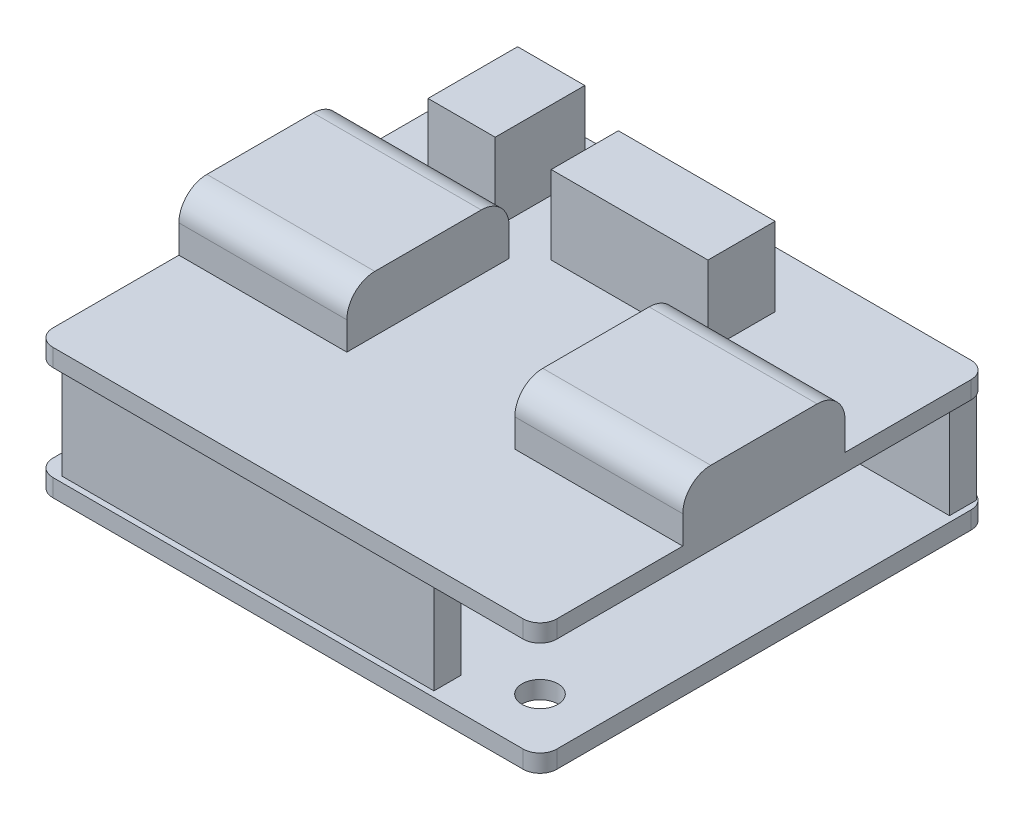
SolidWorks part; units mm, degrees
ref_plane "Front Plane" through (0, 0, 0) normal (0, 0, 1) x (1, 0, 0)
ref_plane "Top Plane" through (0, 0, 0) normal (0, 1, 0) x (1, 0, 0)
ref_plane "Right Plane" through (0, 0, 0) normal (1, 0, 0) x (0, 0, -1)
sketch "Sketch1" plane through (0, 0, 0) normal (0, 1, 0) x (1, 0, 0)
  line L1 (-22.5, -20) -> (22.5, -20)
  line L2 (-22.5, -20) -> (-22.5, 20)
  line L3 (-22.5, 20) -> (22.5, 20)
  line L4 (22.5, -20) -> (22.5, 20)
  line L5 (-22.5, -20) -> (22.5, 20) construction
  line L6 (-22.5, 20) -> (22.5, -20) construction
  point P0 (0, 0)
  dimension "D1" = 45
  dimension "D2" = 40
extrude "Boss-Extrude1" add sketch "Sketch1" along normal blind 1.57
sketch "Sketch2" plane through (0, 1.57, 0) normal (0, 1, 0) x (1, 0, 0)
  line L0 (-21.19, -20) -> (-21.19, 20) construction
  line L1 (21.99, 19.49) -> (-3.92, 19.49)
  line L2 (21.99, 19.49) -> (21.99, 17.08)
  line L3 (21.99, 17.08) -> (-3.92, 17.08)
  line L4 (-3.92, 19.49) -> (-3.92, 17.08)
  line L5 (12.52, -17.08) -> (-20.68, -17.08)
  line L6 (12.52, -17.08) -> (12.52, -19.49)
  line L7 (12.52, -19.49) -> (-20.68, -19.49)
  line L8 (-20.68, -17.08) -> (-20.68, -19.49)
  line L9 (-22.5, -20) -> (22.5, -20) construction
  line L10 (22.5, 20) -> (-22.5, 20) construction
  line L11 (22.5, -20) -> (22.5, 20) construction
  circle A0 centre (17.5, -15) radius 3.2 construction
  dimension "D6" = 6.4
  dimension "D1" = 2.41
  dimension "D2" = 2.41
  dimension "D3" = 33.2
  dimension "D4" = 25.91
  dimension "D5" = 43.69
  dimension "D7" = 5
  dimension "D8" = 5
  dimension "D9" = 0.51
  dimension "D10" = 0.51
  dimension "D11" = 0.51
  dimension "D12" = 0.51
extrude "Boss-Extrude2" add sketch "Sketch2" along normal blind 8.5
sketch "Sketch3" plane through (0, 10.07, 0) normal (0, 1, 0) x (1, 0, 0)
  line L0 (22.5, 20) -> (-22.5, 20) construction
  line L1 (22.5, -20) -> (-22.5, -20)
  line L2 (22.5, -20) -> (22.5, 20)
  line L3 (22.5, 20) -> (-22.5, 20)
  line L4 (-22.5, -20) -> (-22.5, 20)
  dimension "D1" = 45
extrude "Boss-Extrude3" add sketch "Sketch3" along normal blind 1.57
sketch "Sketch4" plane through (0, 11.64, 0) normal (0, 1, 0) x (1, 0, 0)
  line L0 (12.52, -17.08) -> (-20.68, -17.08)
  line L1 (12.52, -17.08) -> (12.52, -19.49)
  line L2 (12.52, -19.49) -> (-20.68, -19.49)
  line L3 (-20.68, -17.08) -> (-20.68, -19.49)
  line L4 (-22.5, -20) -> (22.5, -20) construction
  line L5 (22.5, -20) -> (22.5, 20) construction
  dimension "D1" = 0.51
  dimension "D2" = 2.41
  dimension "D3" = 33.2
  dimension "D4" = 9.98
extrude "Boss-Extrude4" [suppressed] add sketch "Sketch4" along normal blind 8.51
sketch "Sketch5" plane through (0, 11.64, 0) normal (0, 1, 0) x (1, 0, 0)
  line L0 (-22.5, 20) -> (-22.5, -20) construction
  line L1 (-22.5, -7.25) -> (-7.5, -7.25)
  line L2 (-22.5, -7.25) -> (-22.5, 7.25)
  line L3 (-22.5, 7.25) -> (-7.5, 7.25)
  line L4 (-7.5, -7.25) -> (-7.5, 7.25)
  line L5 (-11.0825, 0) -> (11.0825, 0) construction
  point P6 (-7.5, 0)
  dimension "D1" = 14.5
  dimension "D2" = 15
extrude "Boss-Extrude5" add sketch "Sketch5" along normal blind 5
fillet "Fillet1" radius 2.5 2 edges at (-15, 16.64, -7.25) (-15, 16.64, 7.25)
mirror "Mirror1" about plane through (0, 0, 0) normal (1, 0, 0) of "Fillet1", "Boss-Extrude5"
sketch "Sketch7" plane through (0, 1.57, 0) normal (0, 1, 0) x (1, 0, 0)
  line L0 (-22.5, -20) -> (22.5, -20) construction
  line L1 (22.5, -20) -> (22.5, -7.25) construction
  line L2 (-22.5, 20) -> (-22.5, 7.25) construction
  line L3 (22.5, 20) -> (-22.5, 20) construction
  circle A0 centre (17.5, -15) radius 1.6
  circle A1 centre (-17.5, 15) radius 1.6
  dimension "D3" = 3.2
  dimension "D6" = 3.2
  dimension "D1" = 5
  dimension "D2" = 5
  dimension "D4" = 5
  dimension "D5" = 5
extrude "Cut-Extrude1" cut sketch "Sketch7" against normal up to next (1.57 mm away)
fillet "Fillet2" radius 1.5 4 edges at (-22.5, 0.785, -20) (-22.5, 0.785, 20) (22.5, 0.785, 20) (22.5, 0.785, -20)
fillet "Fillet3" radius 1.5 4 edges at (-22.5, 10.855, -20) (22.5, 10.855, 20) (22.5, 10.855, -20) (-22.5, 10.855, 20)
sketch "Sketch8" plane through (0, 11.64, 0) normal (0, 1, 0) x (1, 0, 0)
  line L1 (-5.5, 9) -> (8.5, 9)
  line L2 (-5.5, 9) -> (-5.5, 15)
  line L3 (-5.5, 15) -> (8.5, 15)
  line L4 (8.5, 9) -> (8.5, 15)
  line L5 (21, 20) -> (-21, 20) construction
  line L6 (-22.5, 18.5) -> (-22.5, 7.25) construction
  line L7 (-16.5, 9) -> (-10.5, 9)
  line L8 (-16.5, 9) -> (-16.5, 17)
  line L9 (-16.5, 17) -> (-10.5, 17)
  line L10 (-10.5, 9) -> (-10.5, 17)
  dimension "D1" = 6
  dimension "D2" = 14
  dimension "D3" = 5
  dimension "D4" = 8
  dimension "D5" = 6
  dimension "D6" = 3
  dimension "D7" = 6
  dimension "D8" = 17
extrude "Boss-Extrude6" add sketch "Sketch8" along normal blind 7
